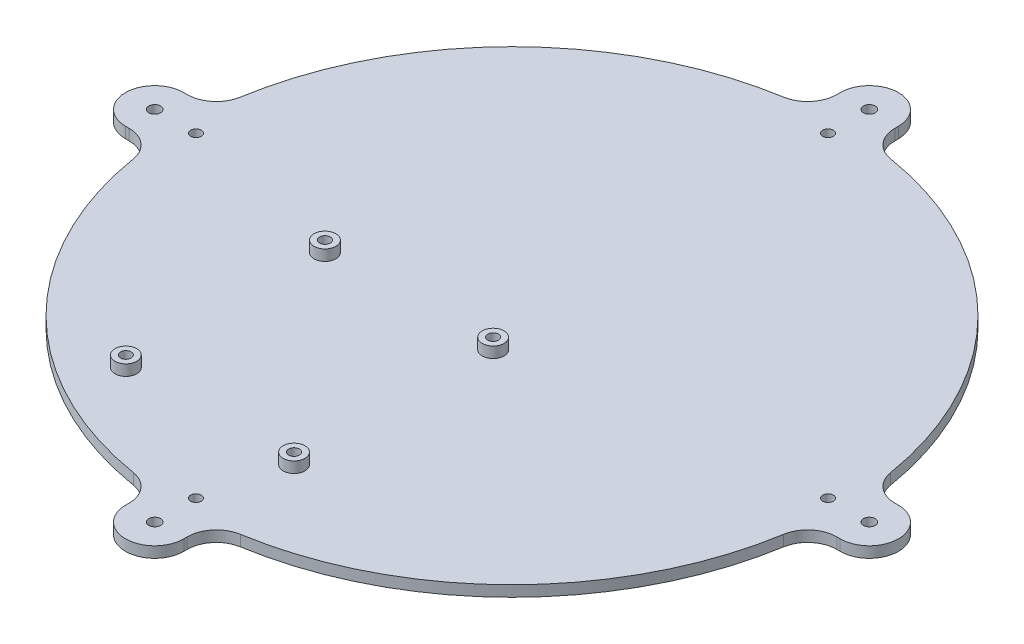
SolidWorks part; units mm, degrees
material "ABS"
ref_plane "Front Plane" through (0, 0, 0) normal (0, 0, 1) x (1, 0, 0)
ref_plane "Top Plane" through (0, 0, 0) normal (0, 1, 0) x (1, 0, 0)
ref_plane "Right Plane" through (0, 0, 0) normal (1, 0, 0) x (0, 0, -1)
sketch "Sketch1" plane through (0, 0, 0) normal (0, 1, 0) x (1, 0, 0)
  line L0 (-8.4836, 95.6244) -> (-8.4836, 104.108)
  line L9 (8.4836, 104.108) -> (8.4836, 95.6244)
  line L10 (104.108, -8.4836) -> (95.6244, -8.4836)
  line L11 (95.6244, 8.4836) -> (104.108, 8.4836)
  line L12 (-8.4836, -104.108) -> (-8.4836, -95.6244)
  line L13 (8.4836, -95.6244) -> (8.4836, -104.108)
  line L14 (-104.108, 8.4836) -> (-95.6244, 8.4836)
  line L15 (-95.6244, -8.4836) -> (-104.108, -8.4836)
  line L16 (0, 0) -> (0, 146.6167) construction
  circle A1 centre (0, 104.108) radius 1.7272
  circle A2 centre (104.108, 0) radius 1.7272
  circle A3 centre (0, -104.108) radius 1.7272
  circle A4 centre (-104.108, 0) radius 1.7272
  arc A6 (-8.4836, 95.6244) -> (-95.6244, 8.4836) centre (0, 0) ccw
  arc A10 (95.6244, 8.4836) -> (8.4836, 95.6244) centre (0, 0) ccw
  arc A11 (8.4836, -95.6244) -> (95.6244, -8.4836) centre (0, 0) ccw
  arc A12 (-95.6244, -8.4836) -> (-8.4836, -95.6244) centre (0, 0) ccw
  arc A13 (8.4836, 104.108) -> (-8.4836, 104.108) centre (0, 104.108) ccw
  arc A14 (104.108, -8.4836) -> (104.108, 8.4836) centre (104.108, 0) ccw
  arc A15 (-8.4836, -104.108) -> (8.4836, -104.108) centre (0, -104.108) ccw
  arc A16 (-104.108, 8.4836) -> (-104.108, -8.4836) centre (-104.108, 0) ccw
  point P17 (0, 0)
  point P36 (0, 0)
  point P44 (0, 0)
  dimension "D1" = 4
  dimension "D2" = 3.4544
  dimension "D4" = 4
  dimension "D5" = 8.4836
  dimension "D6" = 0
  dimension "D9" = 192
  dimension "D3" = 16.9672
extrude "Boss-Extrude1" add sketch "Sketch1" along normal blind 3.175
fillet "Fillet2" radius 8.4836 8 edges at (-8.4836, 1.5875, -95.6244) (8.4836, 1.5875, -95.6244) (95.6244, 1.5875, -8.4836) (95.6244, 1.5875, 8.4836) (8.4836, 1.5875, 95.6244) (-8.4836, 1.5875, 95.6244) (-95.6244, 1.5875, -8.4836) (-95.6244, 1.5875, 8.4836)
sketch "Sketch2" plane through (0, 3.175, 0) normal (0, 1, 0) x (1, 0, 0)
  line L1 (-15.5895, -94.7257) -> (15.5895, -94.7257) construction
  line L2 (5.8257, -69.3257) -> (-43.1743, -69.3257) construction
  line L3 (-43.1743, -69.3257) -> (-43.1743, -11.3257) construction
  line L4 (-43.1743, -11.3257) -> (5.8257, -11.3257) construction
  line L5 (5.8257, -11.3257) -> (5.8257, -69.3257) construction
  circle A1 centre (-43.1743, -69.3257) radius 3.175
  circle A2 centre (-43.1743, -11.3257) radius 3.175
  circle A4 centre (5.8257, -69.3257) radius 3.175
  circle A5 centre (5.8257, -11.3257) radius 3.175
  dimension "D1" = 6.35
  dimension "D2" = 49
  dimension "D4" = 6.35
  dimension "D5" = 58
  dimension "D6" = 6.35
  dimension "D7" = 6.35
  dimension "D8" = 88.9
  dimension "D3" = 50.8
extrude "Boss-Extrude2" add sketch "Sketch2" along normal blind 3.175
hole_wizard "CSK for M2.5 Cross Countersunk Head Screw4" positions "Sketch6" profile "Sketch7" countersink size "M2.5" standard "AS" end condition through all
sketch "Sketch6" plane through (0, 0, 0) normal (0, -1, 0) x (-1, 0, 0)
  point P0 (-5.8257, -11.3257)
  point P3 (43.1743, -11.3257)
  point P6 (43.1743, -69.3257)
  point P9 (-5.8257, -69.3257)
sketch "Sketch7" plane through (5.8257, 0, 11.3257) normal (1, 0, 0) x (0, 0, -1)
  line L0 (0, 0) -> (0, 6.35)
  line L1 (0, 6.35) -> (1.55, 6.35)
  line L2 (1.55, 6.35) -> (1.55, 0.9174)
  line L3 (1.55, 0.9174) -> (2.5, 0)
  line L5 (2.5, 0) -> (0, 0)
  line L6 (-1.55, 0.9174) -> (-2.5, 0) construction
  line L11 (0, -6.35) -> (0, 107.95) construction
  dimension "Thru Hole Dia." = 3.1
  dimension "Thru Hole Depth" = 6.35
  dimension "Near C'Sink Dia." = 5
  dimension "Near C'Sink Angle" = 92
sketch "Sketch8" plane through (0, 3.175, 0) normal (0, 1, 0) x (1, 0, 0)
  line L0 (0, -104.108) -> (0, 104.108) construction
  line L1 (0, 0) -> (104.108, 0) construction
  line L2 (0, 0) -> (-104.108, 0) construction
  circle A0 centre (0, 92.075) radius 2.7341
  circle A1 centre (92.075, 0) radius 2.7341
  circle A2 centre (0, -92.075) radius 2.7341
  arc A3 (94.7257, 15.5895) -> (15.5895, 94.7257) centre (0, 0) ccw construction
  circle A4 centre (-92.075, 0) radius 2.7341
  circle A5 centre (0, 104.108) radius 1.7272 construction
  point P9 (0, 0)
  point P24 (0, 0)
  point P25 (0, 0)
  dimension "D1" = 5.4683
  dimension "D2" = 92.075
  dimension "D3" = 12.033
  dimension "D4" = 4
hole_wizard "CSK for M2.5 Cross Countersunk Head Screw5" positions "Sketch9" profile "Sketch10" countersink size "M2.5" standard "AS" end condition through all
sketch "Sketch9" plane through (0, 0, 0) normal (0, -1, 0) x (-1, 0, 0)
  point P0 (-92.075, 0)
  point P3 (0, 92.075)
  point P6 (92.075, 0)
  point P9 (0, -92.075)
sketch "Sketch10" plane through (92.075, 0, 0) normal (1, 0, 0) x (0, 0, -1)
  line L0 (0, 0) -> (0, 6.35)
  line L1 (0, 6.35) -> (1.55, 6.35)
  line L2 (1.55, 6.35) -> (1.55, 0.9174)
  line L3 (1.55, 0.9174) -> (2.5, 0)
  line L5 (2.5, 0) -> (0, 0)
  line L6 (-1.55, 0.9174) -> (-2.5, 0) construction
  line L11 (0, -6.35) -> (0, 107.95) construction
  dimension "Thru Hole Dia." = 3.1
  dimension "Thru Hole Depth" = 6.35
  dimension "Near C'Sink Dia." = 5
  dimension "Near C'Sink Angle" = 92
